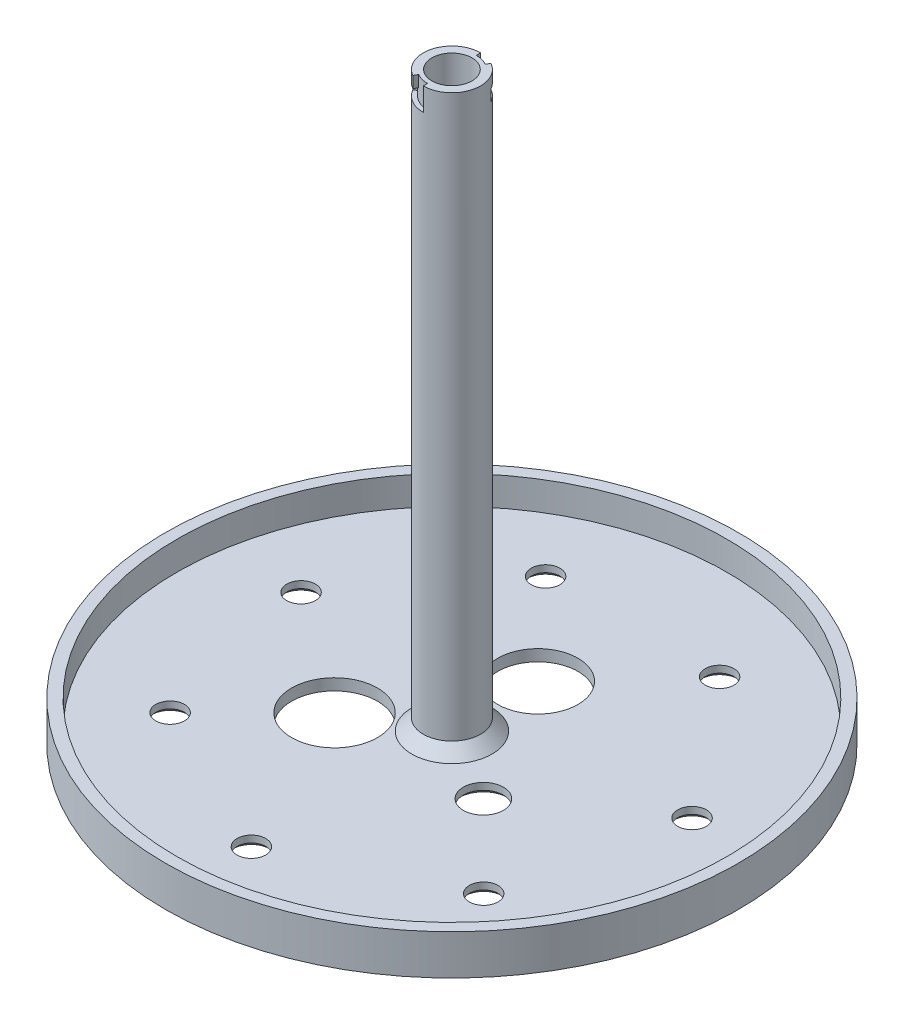
SolidWorks part; units mm, degrees
ref_plane "Front Plane" through (0, 0, 0) normal (0, 0, 1) x (1, 0, 0)
ref_plane "Top Plane" through (0, 0, 0) normal (0, 1, 0) x (1, 0, 0)
ref_plane "Right Plane" through (0, 0, 0) normal (1, 0, 0) x (0, 0, -1)
sketch "Sketch1" plane through (0, 0, 0) normal (0, 1, 0) x (1, 0, 0)
  line L0 (0, 15) -> (0, 0) construction
  line L1 (0, 0) -> (-12.9904, -7.5) construction
  line L2 (0, 0) -> (12.9904, -7.5) construction
  circle A0 centre (0, 0) radius 48
  circle A1 centre (0, 15) radius 7
  circle A2 centre (-12.9904, -7.5) radius 7.5
  circle A3 centre (12.9904, -7.5) radius 3.5
  circle A4 centre (0, 0) radius 3.5
  point P3 (0, 15)
  point P8 (12.9904, -7.5)
  point P9 (-12.9904, -7.5)
  point P10 (0, 0)
  dimension "D1" = 96
  dimension "D4" = 14
  dimension "D5" = 15
  dimension "D6" = 7
  dimension "D7" = 7
  dimension "D2" = 15
  dimension "D3" = 3
extrude "Boss-Extrude1" add sketch "Sketch1" along normal blind 2
sketch "Sketch2" plane through (0, 2, 0) normal (0, 1, 0) x (1, 0, 0)
  line L0 (0, 0) -> (12.9904, -7.5) construction
  line L1 (0, 0) -> (0, 48) construction
  line L2 (0, 0) -> (-12.9904, -7.5) construction
  line L3 (0, 0) -> (-41.5692, -24) construction
  line L4 (0, 0) -> (41.5692, -24) construction
  circle A0 centre (0, 0) radius 48 construction
  circle A1 centre (-12.9904, -7.5) radius 7.5 construction
  circle A2 centre (12.9904, -7.5) radius 3.5 construction
  circle A3 centre (0, 0) radius 25
  circle A4 centre (21.6506, -12.5) radius 3
  circle A5 centre (-21.6506, -12.5) radius 3
  circle A6 centre (0, 25) radius 3
  point P22 (0, 0)
  dimension "D1" = 50
  dimension "D2" = 6
  dimension "D3" = 3
ref_plane "Plane1" through (0, 0, 0) normal (-0.5, 0, -0.866) x (-0.866, 0, 0.5)
sketch "Sketch3" plane through (0, 2, 0) normal (0, 1, 0) x (1, 0, 0)
  circle A0 centre (0, 0) radius 3.5
  circle A1 centre (0, 0) radius 5
  dimension "D1" = 10
extrude "Boss-Extrude2" add sketch "Sketch3" along normal blind 100
sketch "Sketch6" plane through (0, 0, 0) normal (0, -1, 0) x (1, 0, 0)
  circle A0 centre (0, 0) radius 35
  circle A1 centre (0, 35) radius 2.5
  circle A2 centre (27.3641, 21.8221) radius 2.5
  circle A3 centre (34.1225, -7.7882) radius 2.5
  circle A4 centre (15.1859, -31.5339) radius 2.5
  circle A5 centre (-15.1859, -31.5339) radius 2.5
  circle A6 centre (-34.1225, -7.7882) radius 2.5
  circle A7 centre (-27.3641, 21.8221) radius 2.5
  point P20 (0, 0)
  dimension "D1" = 70
  dimension "D2" = 5
  dimension "D3" = 7
extrude "Cut-Extrude2" cut sketch "Sketch6" against normal up to next contours A0 A4 | A0 A4 | A0 A3 | A0 A3 | A0 A2 | A0 A2 | A0 A1 | A0 A1 | A0 A7 | A0 A7 | A0 A6 | A0 A6 | A0 A5 | A0 A5 region at (26.5221, 0, 21.1507) region at (28.181, 0, 22.4736) region at (35.1411, 0, -8.0207) region at (33.0725, 0, -7.5486) region at (0, 0, 33.923) region at (0, 0, 36.0448) region at (15.6392, 0, -32.4752) region at (14.7187, 0, -30.5636) region at (-26.5221, 0, 21.1507) region at (-28.181, 0, 22.4736) region at (-15.6392, 0, -32.4752) region at (-14.7187, 0, -30.5636) region at (-33.0725, 0, -7.5486) region at (-35.1411, 0, -8.0207)
chamfer "Chamfer2" distance 0.8 angle 45 8 edges at (0, 0, 32.5) (-27.3641, 0, 19.3221) (-34.1225, 0, -10.2882) (-15.1859, 0, -34.0339) (27.3641, 0, 19.3221) (12.9904, 0, 11) (34.1225, 0, -10.2882) (15.1859, 0, -34.0339)
ref_axis "Axis1" through (0, 102, 0) along (0, -1, 0)
sketch "Sketch7" plane through (0, 0, 0) normal (1, 0, 0) x (0, 0, -1)
  line L1 (5, 102) -> (4.25, 102)
  line L2 (5, 102) -> (5, 100)
  line L3 (5, 100) -> (4.25, 100)
  line L4 (4.25, 102) -> (4.25, 100)
  line L5 (5, 100) -> (4.25, 100)
  line L6 (5, 100) -> (5, 98)
  line L7 (5, 98) -> (4.25, 98)
  line L8 (4.25, 100) -> (4.25, 98)
  dimension "D1" = 2
  dimension "D2" = 0.75
  dimension "D3" = 2
  dimension "D4" = 0.75
revolve "Cut-Revolve1" cut sketch "Sketch7" angle 30 about axis through (0, 102, 0) along (0, -1, 0) region at (0, 101, -4.625)
revolve "Cut-Revolve2" cut sketch "Sketch7<4>" angle 60 about axis through (0, 102, 0) along (0, -1, 0) region at (0, 99, -4.625)
sketch "Sketch7<4>" plane through (0, 0, 0) normal (1, 0, 0) x (0, 0, -1) same geometry as "Sketch7"
pattern_circular "CirPattern5" count 2 over 360 about axis through (0, 102, 0) along (0, -1, 0) of "Cut-Revolve2", "Cut-Revolve1"
sketch "Sketch8" plane through (0, 2, 0) normal (0, 1, 0) x (1, 0, 0)
  circle A0 centre (0, 0) radius 50
  circle A1 centre (0, 0) radius 48
  dimension "D1" = 100
  dimension "D2" = 96
extrude "Boss-Extrude3" add sketch "Sketch8" along normal blind 5 and the other way blind 2 separate body
chamfer "Chamfer3" distance 2 angle 45 1 edges at (0, 2, 5)
